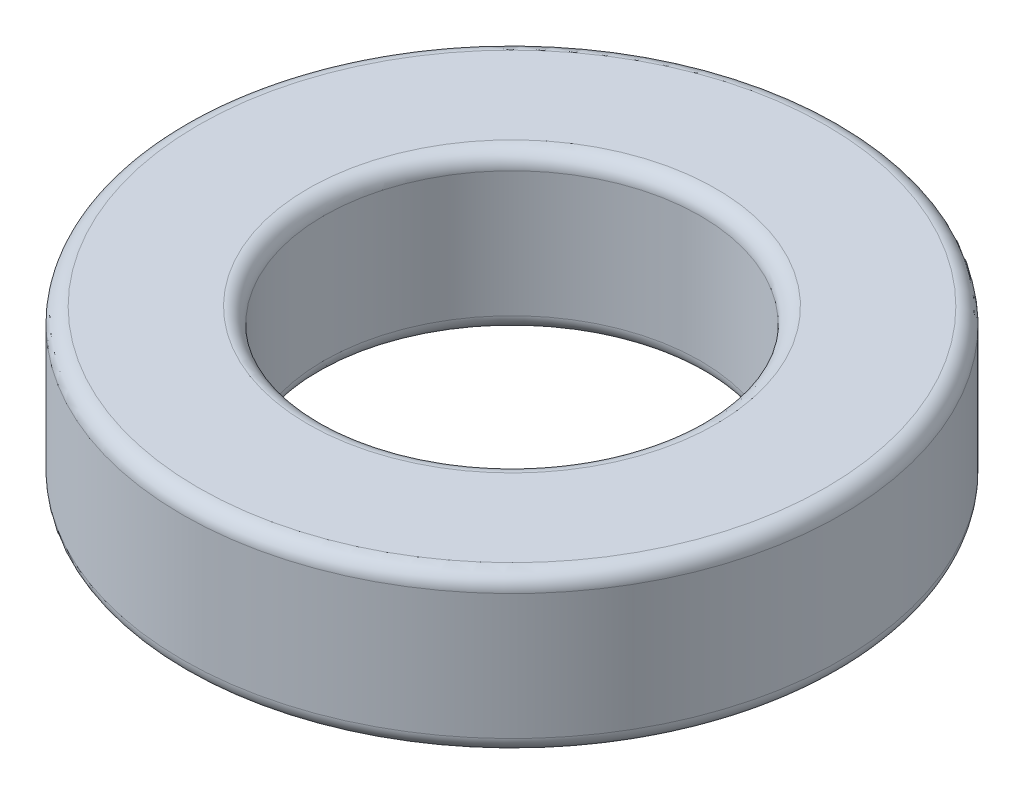
SolidWorks part; units mm, degrees
ref_plane "Спереди" through (0, 0, 0) normal (0, 0, 1) x (1, 0, 0)
ref_plane "Сверху" through (0, 0, 0) normal (0, 1, 0) x (1, 0, 0)
ref_plane "Справа" through (0, 0, 0) normal (1, 0, 0) x (0, 0, -1)
sketch "Эскиз1" plane through (0, 0, 0) normal (0, 1, 0) x (1, 0, 0)
  circle A0 centre (0, 0) radius 6
  circle A1 centre (0, 0) radius 10.5
  dimension "D1" = 12
  dimension "D2" = 21
extrude "Бобышка-Вытянуть1" add sketch "Эскиз1" along normal blind 5
fillet "Скругление1" radius 0.5 4 edges at (0, 5, 6) (0, 0, 6) (0, 0, 10.5) (0, 5, 10.5)
